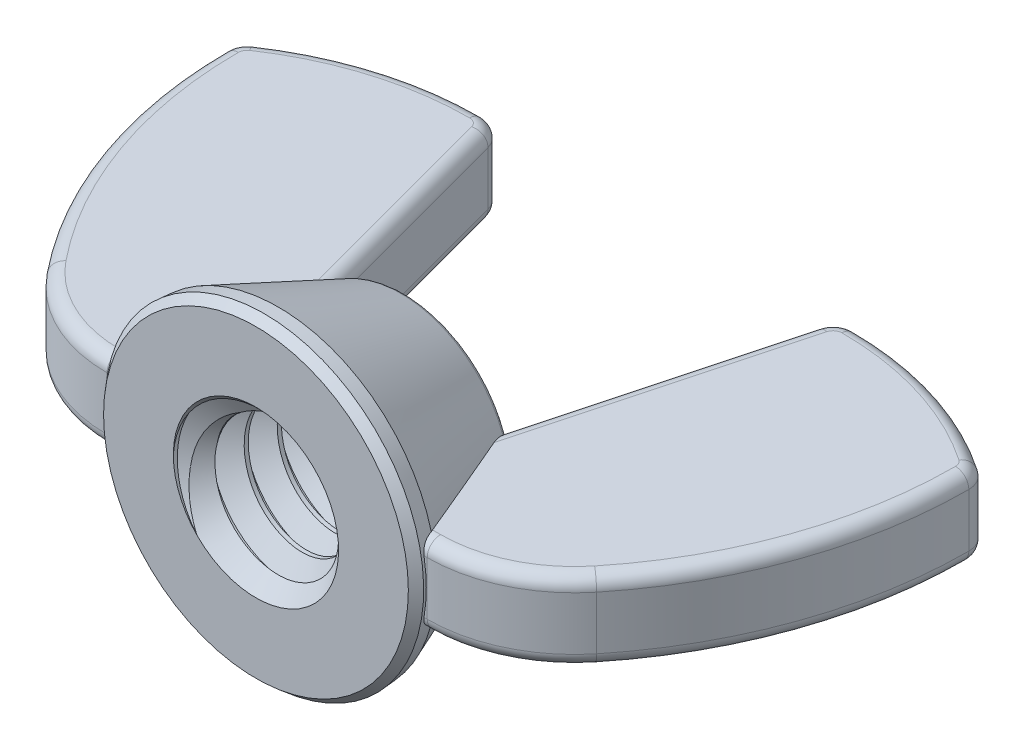
SolidWorks part; units mm, degrees
ref_plane "Front Plane" through (0, 0, 0) normal (0, 0, 1) x (1, 0, 0)
ref_plane "Top Plane" through (0, 0, 0) normal (0, 1, 0) x (1, 0, 0)
ref_plane "Right Plane" through (0, 0, 0) normal (1, 0, 0) x (0, 0, -1)
sketch "Sketch1" plane through (0, 0, 0) normal (0, 0, 1) x (1, 0, 0)
  circle A0 centre (0, 0) radius 3.175
  circle A1 centre (0, 0) radius 6.1516
  dimension "D1" = 12.3031
  dimension "thread dia" = 6.35
sketch "Sketch2" plane through (0, 0, 0) normal (0, 1, 0) x (1, 0, 0)
  line L0 (0, 0) -> (0, 15.875) construction
  line L1 (-3.175, 0) -> (3.175, 0) construction
  line L2 (-14.2875, 15.875) -> (14.2875, 15.875) construction
  line L3 (14.2875, 15.875) -> (14.2875, 0) construction
  line L4 (-14.2875, 15.875) -> (-14.2875, 0) construction
  line L5 (-14.2875, 0) -> (14.2875, 0) construction
  line L6 (-4.1928, 5.715) -> (4.1928, 5.715) construction
  line L7 (0, 0) -> (0, 5.715) construction
  line L8 (-4.3144, 0.8572) -> (6.1516, 0.8572) construction
  line L9 (6.1516, 0) -> (6.1516, 5.715) construction
  line L10 (3.7735, 5.715) -> (6.5552, 16.0963)
  line L12 (4.1928, 5.715) -> (4.1928, 0.4286) construction
  line L13 (-6.1516, 0) -> (6.1516, 0) construction
  line L14 (6.1516, 0.8572) -> (4.1928, 5.715) construction
  line L15 (6.5552, 16.0963) -> (14.6189, 13.631)
  line L16 (14.6189, 13.631) -> (8.5296, 0.4286)
  line L17 (6.1516, 0.4286) -> (8.5296, 0.4286)
  line L19 (3.7735, 0.4286) -> (6.1516, 0.4286)
  line L20 (-3.7735, 5.715) -> (3.7735, 5.715) construction
  line L21 (3.7735, 5.715) -> (3.7735, 0.4286)
  circle A3 centre (13.4331, 13.1001) radius 0.8544 construction
  circle A4 centre (7.1515, 15.0206) radius 0.8544 construction
  dimension "D6" = 1.7088
  dimension "D7" = 15
  dimension "D1" = 0.8572
  dimension "A" = 28.575
  dimension "B" = 15.875
  dimension "D2" = 5.715
  dimension "D3" = 21.96
  dimension "D4" = 8.3857
  dimension "D5" = 0.4286
  dimension "D8" = 17
  dimension "D9" = 7.5471
sketch "Sketch13" plane through (0, 0, 0) normal (0, 1, 0) x (1, 0, 0)
  line L1 (3.7735, 5.715) -> (3.7735, 0.4286) construction
  line L2 (3.7735, 5.715) -> (6.5552, 16.0963) construction
  line L3 (-14.2875, 15.875) -> (14.2875, 15.875) construction
  line L4 (14.2875, 15.875) -> (14.2875, 0) construction
  line L5 (6.1516, 0.4286) -> (8.5296, 0.4286) construction
  line L6 (3.7735, 0.4286) -> (6.1516, 0.4286) construction
  line L7 (0, 0) -> (0, 5.715) construction
  line L8 (-3.175, 0) -> (3.175, 0) construction
  line L9 (0, 0) -> (0, 15.875) construction
  line L10 (-4.1928, 5.715) -> (4.1928, 5.715) construction
  line L11 (3.7735, 0.4286) -> (6.1516, 0.4286)
  line L12 (3.7735, 5.715) -> (3.7735, 0.4286)
  line L13 (3.7735, 5.715) -> (6.3262, 15.2417)
  circle A0 centre (13.4331, 13.1001) radius 0.8544 construction
  circle A1 centre (7.1515, 15.0206) radius 0.8544 construction
  arc A5 (14.2875, 13.1001) -> (13.9109, 13.8084) centre (13.4331, 13.1001) ccw
  arc A6 (7.1515, 15.875) -> (6.3262, 15.2417) centre (7.1515, 15.0206) ccw
  arc A7 (10.5535, 2.5321) -> (14.2875, 13.1001) centre (-2.5346, 13.1001) ccw
  arc A8 (13.9109, 13.8084) -> (7.1515, 15.875) centre (7.1515, 3.7873) ccw
  arc A10 (6.1516, 0.4286) -> (10.5535, 2.5321) centre (6.1516, 6.0864) ccw
extrude "Extrude2" add sketch "Sketch13" along normal mid plane 3.0758
sketch "Sketch3" plane through (0, 0, 0) normal (0, 0, 1) x (1, 0, 0)
  circle A0 centre (0, 0) radius 6.1516 construction
  circle A1 centre (0, 0) radius 6.1516
extrude "Extrude1" add sketch "Sketch3" against normal up to vertex (0.8572 mm away) draft 5 separate body up to point (6.1516, 0, -0.8572)
sketch "Sketch15" plane through (0, 0, -0.8572) normal (0, 0, -1) x (-1, 0, 0)
  circle A1 centre (0, 0) radius 6.0766
  circle A2 centre (0, 0) radius 6.0766
  dimension "D1" = 0
extrude "Extrude3" add sketch "Sketch15" along normal up to vertex (4.8578 mm away) draft 21.96 up to point (0, 0, -5.715)
fillet "Fillet3" radius 0.254 1 edges at (-4.1178, 0, -5.715)
sketch "Sketch12" plane through (0, 0, -5.715) normal (0, 0, -1) x (-1, 0, 0)
  circle A1 centre (0, 0) radius 6.0766
  circle A2 centre (0, 0) radius 6.0766 construction
  dimension "D1" = 12.1531
sketch "Sketch4" plane through (0, 0, 0) normal (0, 0, 1) x (1, 0, 0)
  circle A0 centre (0, 0) radius 3.175 construction
  circle A1 centre (0, 0) radius 3.175
extrude "Cut-Extrude1" cut sketch "Sketch4" against normal through all
sketch "Sketch5" plane through (0, 0, 0) normal (0, 0, 1) x (1, 0, 0)
  circle A0 centre (0, 0) radius 3.175 construction
  circle A1 centre (0, 0) radius 3.175
curve "Helix/Spiral1" pitch 1.27 height 8.89 turns 7 parameters "pitch"=1.27
sketch "Sketch6" plane through (0, 0, 0) normal (0, 1, 0) x (1, 0, 0)
  line L0 (-3.175, -1.1112) -> (-2.3501, -0.635)
  line L1 (-2.3501, -0.635) -> (-2.3501, -0.4762)
  line L2 (-2.3501, -0.4762) -> (-3.175, 0)
  line L3 (-3.175, -1.1112) -> (-3.175, 0)
  line L4 (-3.175, -0.5556) -> (-2.3501, -0.5556) construction
  line L5 (-2.7626, -0.8731) -> (-2.7626, -0.2381) construction
  line L6 (-3.175, 0) -> (3.175, 0) construction
  dimension "D1" = 60
  dimension "D2" = 0.1588
  dimension "D3" = 0.635
sweep "Sweep1" add profiles "Sketch6" path "Helix/Spiral1"
sketch "Sketch7" plane through (0, 0, 0) normal (0, 0, 1) x (1, 0, 0)
  circle A1 centre (0, 0) radius 6.1516
  circle A2 centre (0, 0) radius 6.1516
  dimension "D1" = 0
extrude "Cut-Extrude2" cut sketch "Sketch7" along normal through all
ref_plane "Plane1" through (0, 0, -5.715) normal (0, 0, 1) x (1, 0, 0)
sketch "Sketch8" plane through (0, 0, -5.715) normal (0, 0, 1) x (1, 0, 0)
  circle A0 centre (0, 0) radius 6.0766 construction
  circle A2 centre (0, 0) radius 6.0766
extrude "Cut-Extrude3" cut sketch "Sketch8" against normal through all
sketch "Sketch9" plane through (0, 0, 0) normal (0, 0, 1) x (1, 0, 0)
  circle A1 centre (0, 0) radius 3.175
  circle A2 centre (0, 0) radius 3.175
  dimension "D1" = 0
extrude "Cut-Extrude4" cut sketch "Sketch9" against normal through all draft 45
sketch "Sketch11" plane through (0, 0, -5.715) normal (0, 0, 1) x (1, 0, 0)
  circle A0 centre (0, 0) radius 3.175 construction
  circle A1 centre (0, 0) radius 3.1242
  circle A2 centre (0, 0) radius 3.175 construction
  dimension "D1" = 0.0508
extrude "Cut-Extrude5" cut sketch "Sketch11" along normal through all draft 45
chamfer "Chamfer1" distance 0.3215 angle 45 1 edges at (6.1516, 0, 0)
fillet "Fillet4" radius 0.5126 14 edges at (4.9626, 1.5379, -0.4286) (8.5909, 1.5379, -0.9815) (6.6314, 1.5379, -15.6984) (10.6856, 1.5379, -15.3468) (14.1875, 1.5379, -13.5012) (4.9626, -1.5379, -0.4286) (8.5909, -1.5379, -0.9815) (6.6314, -1.5379, -15.6984) (10.6856, -1.5379, -15.3468) (14.1875, -1.5379, -13.5012) (13.3266, 1.5379, -7.496) (13.3266, -1.5379, -7.496) (5.0499, 1.5379, -10.4784) (5.0499, -1.5379, -10.4784)
mirror "Mirror6" about plane through (0, 0, 0) normal (1, 0, 0) of bodies 108 113
combine bodies "Combine2" operation type add bodies to combine 116 108 107
equation "\"D1@Sketch1\" = \"thread dia@Sketch1\"*1.725"
equation "\"D2@Sketch2\" = \"B@Sketch2\"*.36"
equation "\"D3@Helix/Spiral1\" = \"D2@Sketch2\"+.125"
equation "\"D2@Sketch6\" = \"pitch@Helix/Spiral1\"*.125"
equation "\"D3@Sketch6\" = \"pitch@Helix/Spiral1\"*.5"
equation "\"D4@Sketch2\" = \"D1@Sketch12\"*.69"
equation "\"D1@Extrude2\" = \"D1@Sketch1\"*.25"
equation "\"D1@Sketch2\" = \"D2@Sketch2\"*.150"
equation "\"D5@Sketch2\" = \"D1@Sketch2\"/2"
equation "\"D3@Extrude3\" = \"D3@Sketch2\""
equation "\"D1@Chamfer1\" = \"D5@Sketch2\"*.75"
equation "\"D9@Sketch2\" = \"D4@Sketch2\"*.9"
equation "\"D6@Sketch2\" = \"D1@Extrude2\"/1.8"
equation "\"D1@Fillet4\" = \"D1@Extrude2\"/6"
